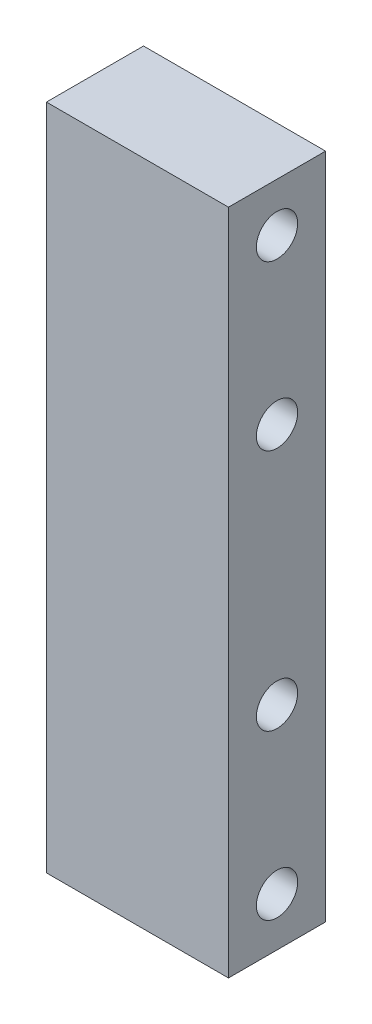
SolidWorks part; units mm, degrees
ref_plane "Front Plane" through (0, 0, 0) normal (0, 0, 1) x (1, 0, 0)
ref_plane "Top Plane" through (0, 0, 0) normal (0, 1, 0) x (1, 0, 0)
ref_plane "Right Plane" through (0, 0, 0) normal (1, 0, 0) x (0, 0, -1)
sketch "Sketch1" plane through (0, 0, 0) normal (1, 0, 0) x (0, 0, -1)
  line L1 (0, 0) -> (8, 0)
  line L2 (0, 0) -> (0, 55)
  line L3 (0, 55) -> (8, 55)
  line L4 (8, 0) -> (8, 55)
  dimension "D1" = 55
  dimension "D2" = 8
extrude "Boss-Extrude1" add sketch "Sketch1" along normal blind 15
hole_wizard "M3 Clearance Hole1" positions "Sketch2" profile "Sketch3" hole size "M3" standard "ANSI Metric" end condition through all
sketch "Sketch2" plane through (15, 0, 0) normal (1, 0, 0) x (0, 0, -1)
  point P0 (4, 51)
  point P3 (4, 37.5)
  point P6 (4, 17.5)
  point P9 (4, 4)
sketch "Sketch3" plane through (15, 51, -4) normal (0, 1, 0) x (0, 0, -1)
  line L0 (0, 0) -> (0, 15)
  line L1 (0, 15) -> (1.7, 15)
  line L2 (1.7, 15) -> (1.7, 0)
  line L5 (1.7, 0) -> (0, 0)
  line L11 (0, -6.35) -> (0, 107.95) construction
  dimension "Thru Hole Dia." = 3.4
  dimension "Thru Hole Depth" = 15
sketch "Sketch5" plane through (0, 0, -8) normal (0, 0, -1) x (-1, 0, 0)
  line L0 (-8.6835, 49.2225) -> (-8.6835, 2.6976) construction
  text T0 "Tool Board Extension"
extrude "Cut-Extrude1" cut sketch "Sketch5" against normal blind 1
